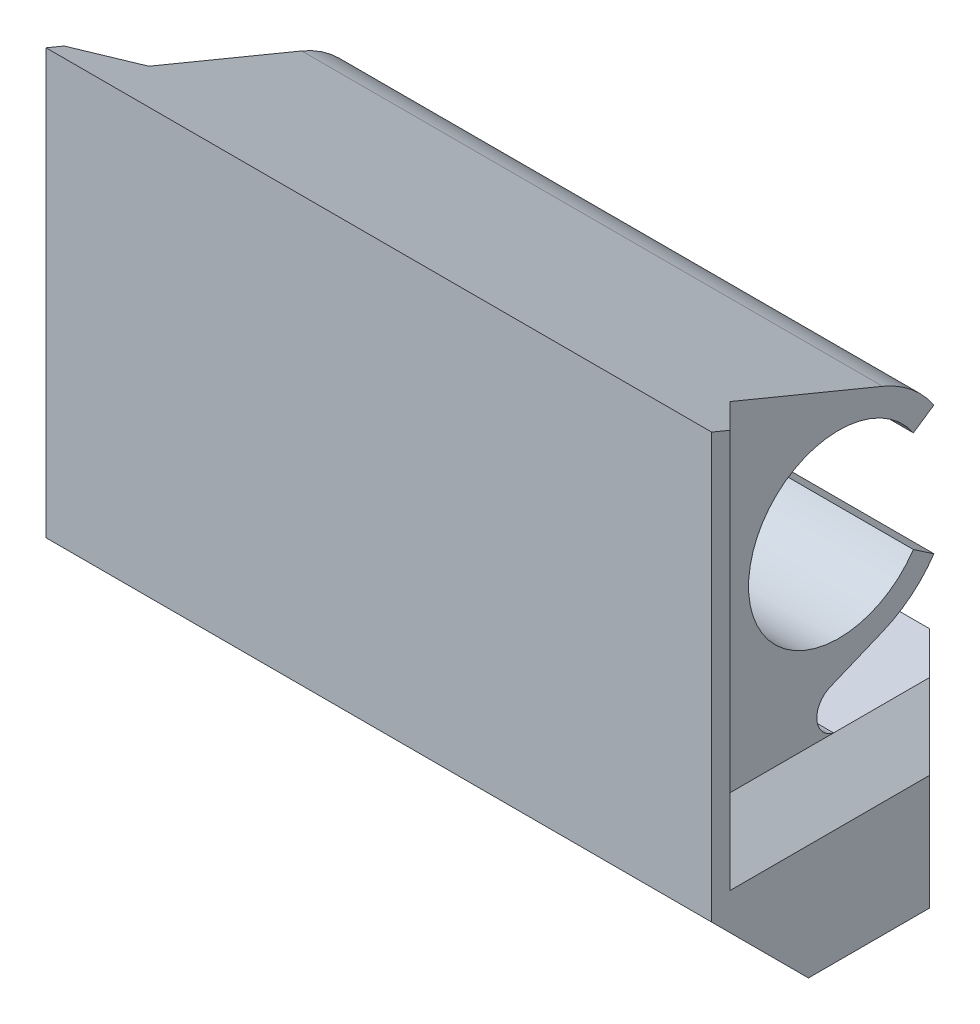
SolidWorks part; units mm, degrees
ref_plane "Front Plane" through (0, 0, 0) normal (0, 0, 1) x (1, 0, 0)
ref_plane "Top Plane" through (0, 0, 0) normal (0, 1, 0) x (1, 0, 0)
ref_plane "Right Plane" through (0, 0, 0) normal (1, 0, 0) x (0, 0, -1)
sketch "Sketch1" plane through (0, 0, 0) normal (0, 0, 1) x (1, 0, 0)
  line L1 (-10.3542, -6.2205) -> (44.6458, -6.2205)
  line L2 (-10.3542, -6.2205) -> (-10.3542, 38.7795)
  line L3 (-10.3542, 38.7795) -> (44.6458, 38.7795)
  line L4 (44.6458, -6.2205) -> (44.6458, 38.7795)
  dimension "D1" = 55
  dimension "D2" = 45
extrude "Boss-Extrude1" add sketch "Sketch1" along normal blind 5 contours L3 L4 L1 L2
sketch "Sketch3" plane through (0, 0, 0) normal (0, 0, -1) x (-1, 0, 0)
  line L0 (10.3542, -6.2205) -> (10.3542, 38.7795) construction
  line L1 (-44.6458, -6.2205) -> (10.3542, -6.2205)
  line L2 (-44.6458, -6.2205) -> (-44.6458, 6.7795)
  line L3 (-44.6458, 6.7795) -> (10.3542, 6.7795)
  line L4 (10.3542, -6.2205) -> (10.3542, 6.7795)
  dimension "D1" = 13
extrude "Boss-Extrude5" add sketch "Sketch3" along normal blind 20 contours L3 L4 L1 L2
chamfer "Chamfer1" distance 8 angle 45 1 edges at (17.1458, -6.2205, 5)
sketch "Sketch5" plane through (0, -6.2205, 0) normal (0, -1, 0) x (1, 0, 0)
  line L0 (44.6458, -20) -> (-10.3542, -20) construction
  line L1 (-10.3542, -3) -> (-10.3542, -20) construction
  circle A0 centre (-0.3542, -11) radius 4.5
  circle A1 centre (34.6458, -11) radius 4.5
  dimension "D1" = 35
  dimension "D2" = 9
  dimension "D3" = 10
extrude "Cut-Extrude2" cut sketch "Sketch5" against normal blind 8
sketch "Sketch6" plane through (-10.3542, 0, 0) normal (-1, 0, 0) x (0, 0, 1)
  line L0 (0, 6.7795) -> (0, 38.7795) construction
  line L1 (-20, 6.7795) -> (0, 6.7795) construction
  line L2 (-8.3082, 10.2139) -> (-12.6292, 12.0001)
  line L3 (-18.5, 20.7795) -> (-16.45, 20.7795) construction
  line L4 (0, 34.7795) -> (-12.6292, 29.559)
  line L5 (-16.1429, 18.6625) -> (-18.1084, 18.08)
  line L6 (-16.1429, 22.8965) -> (-18.1084, 23.479)
  line L7 (0, 34.7795) -> (0, 6.7795)
  line L8 (-1.55, 20.7795) -> (7.8073, 20.7795) construction
  line L10 (0, 6.7795) -> (-8.5765, 6.7795)
  arc A0 (-16.1429, 18.6625) -> (-16.1429, 22.8965) centre (-9, 20.7795) ccw
  arc A1 (-18.1084, 18.08) -> (-12.6292, 12.0001) centre (-9, 20.7795) ccw
  arc A2 (-12.6292, 29.559) -> (-18.1084, 23.479) centre (-9, 20.7795) ccw
  arc A3 (-8.5765, 6.7795) -> (-8.3082, 10.2139) centre (-9, 8.5403) ccw
  dimension "D1" = 9
  dimension "D2" = 14
ref_plane "Plane1" through (-6.8542, 0, 0) normal (-1, 0, 0) x (0, 0, 1)
sketch "Sketch7" plane through (-6.8542, 0, 0) normal (-1, 0, 0) x (0, 0, 1)
  line L1 (-20, 6.7795) -> (0, 6.7795) construction
  point P0 (0, 0)
  point P14 (0, 0)
  line B0 (-8.3082, 10.2139) -> (-12.6292, 12.0001)
  line B1 (-18.5, 20.7795) -> (-16.45, 20.7795) construction
  line B2 (0, 34.7795) -> (-12.6292, 29.559)
  line B3 (0, 34.7795) -> (0, 6.7795)
  line B4 (0, 6.7795) -> (-8.5765, 6.7795)
  arc B5 (-15.171, 16.6056) -> (-15.171, 24.9535) centre (-9, 20.7795) ccw
  arc B6 (-16.869, 15.4571) -> (-12.6292, 12.0001) centre (-9, 20.7795) ccw
  arc B7 (-12.6292, 29.559) -> (-16.869, 26.102) centre (-9, 20.7795) ccw
  arc B8 (-8.5765, 6.7795) -> (-8.3082, 10.2139) centre (-9, 8.5403) ccw
  line B9 (-15.171, 16.6056) -> (-16.869, 15.4571)
  line B10 (-15.171, 24.9535) -> (-16.869, 26.102)
sketch_block_instance "Block1-1"
sketch_block "Block1"
extrude "Boss-Extrude7" add sketch "Sketch7" against normal blind 48
sketch "Sketch8" plane through (-10.3542, 0, 0) normal (-1, 0, 0) x (0, 0, 1)
  line L0 (0, 34.7795) -> (5, 36.8464)
  line L1 (5, 1.7795) -> (5, 38.7795) construction
  line L2 (0, 34.7795) -> (-12.6292, 29.559) construction
  line L3 (5, 36.8464) -> (5, 38.7795)
  line L4 (5, 38.7795) -> (0, 38.7795)
  line L5 (0, 38.7795) -> (0, 34.7795)
extrude "Cut-Extrude3" cut sketch "Sketch8" against normal through all
chamfer "Chamfer2" distance 3.5 angle 45 2 edges at (-10.3542, 6.7795, -10) (-10.3542, 20.7795, 0)
chamfer "Chamfer3" distance 3.5 angle 45 2 edges at (44.6458, 20.7795, 0) (44.6458, 6.7795, -10)
chamfer "Chamfer4" distance 7 angle 45 2 edges at (44.6458, -1.4705, -20) (-10.3542, -1.4705, -20)
sketch "Sketch9" plane through (-6.8542, 0, 0) normal (-1, 0, 0) x (0, 0, 1)
  line L0 (-15.171, 24.9535) -> (-12.3133, 23.0206)
  line L1 (-15.171, 16.6056) -> (-12.3133, 18.5385)
  arc A0 (-15.171, 16.6056) -> (-15.171, 24.9535) centre (-9, 20.7795) ccw
  arc A1 (-12.3133, 18.5385) -> (-12.3133, 23.0206) centre (-9, 20.7795) ccw
extrude "Boss-Extrude8" add sketch "Sketch9" against normal blind 3 contours A1 L0 A0 L1
